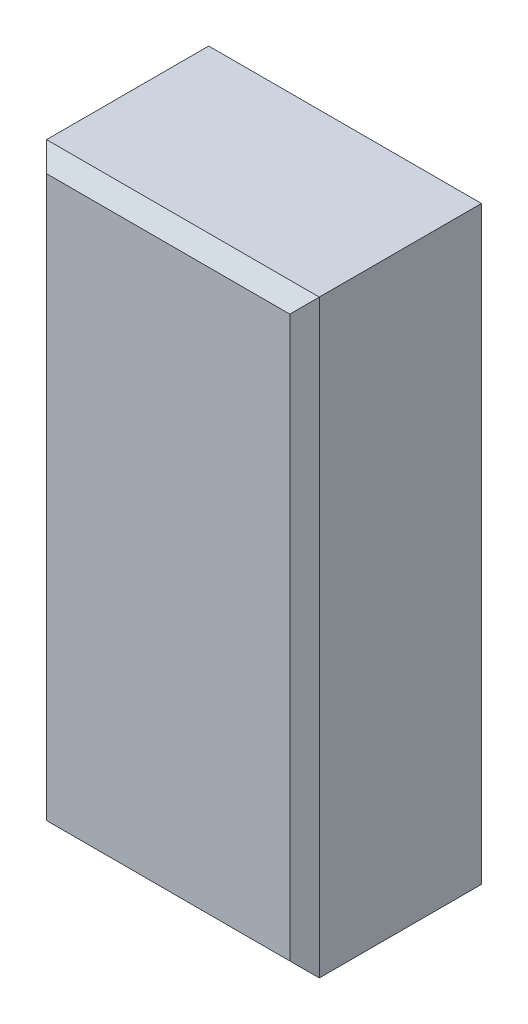
SolidWorks part; units mm, degrees
ref_plane "Front Plane" through (0, 0, 0) normal (0, 0, 1) x (1, 0, 0)
ref_plane "Top Plane" through (0, 0, 0) normal (0, 1, 0) x (1, 0, 0)
ref_plane "Right Plane" through (0, 0, 0) normal (1, 0, 0) x (0, 0, -1)
sketch "Sketch1" plane through (0, 0, 0) normal (0, 0, 1) x (1, 0, 0)
  line L1 (-9.25, 20) -> (9.25, 20)
  line L2 (-9.25, 20) -> (-9.25, -20)
  line L3 (-9.25, -20) -> (9.25, -20)
  line L4 (9.25, 20) -> (9.25, -20)
  line L5 (-9.25, 20) -> (9.25, -20) construction
  line L6 (-9.25, -20) -> (9.25, 20) construction
  point P0 (0, 0)
  dimension "D1" = 18.5
  dimension "D2" = 40
extrude "Boss-Extrude1" add sketch "Sketch1" along normal blind 13
chamfer "Chamfer1" distance 1 angle 45 8 edges at (0, 20, 0) (-9.25, 0, 0) (0, -20, 0) (9.25, 0, 0) (0, -20, 13) (-9.25, 0, 13) (0, 20, 13) (9.25, 0, 13)
equation "\"thiccnes\"=9.5"
equation "\"D1@Boss-Extrude1\"=\"thiccnes\""
